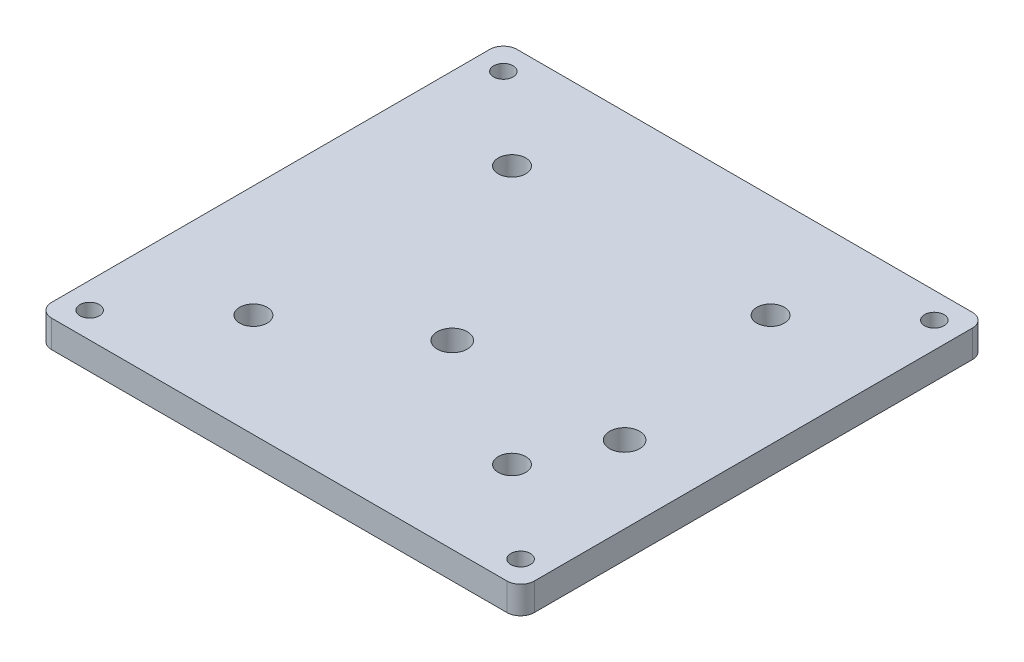
SolidWorks part; units mm, degrees
material "AISI 4130 Steel, annealed at 865C"
ref_plane "Front Plane" through (0, 0, 0) normal (0, 0, 1) x (1, 0, 0)
ref_plane "Top Plane" through (0, 0, 0) normal (0, 1, 0) x (1, 0, 0)
ref_plane "Right Plane" through (0, 0, 0) normal (1, 0, 0) x (0, 0, -1)
sketch "Sketch1" plane through (0, 0, 0) normal (0, 1, 0) x (1, 0, 0)
  line L0 (7, -7) -> (7, -37) construction
  line L1 (0, 0) -> (44, 0)
  line L2 (0, 0) -> (0, -44)
  line L3 (0, -44) -> (44, -44)
  line L4 (44, 0) -> (44, -44)
  line L5 (37, -7) -> (7, -7) construction
  line L6 (40, 2.5) -> (40, 0) construction
  line L7 (22, 0) -> (22, -44) construction
  line L8 (44, 0) -> (51.18, 0)
  line L9 (51.18, 0) -> (51.18, -44)
  line L10 (51.18, -44) -> (44, -44)
  line L11 (22, -22) -> (-15.2405, -22) construction
  line L12 (21.07, -28) -> (41.07, -28) construction
  line L13 (40, -46.5) -> (40, -44) construction
  line L15 (0, -44) -> (44, -44)
  line L16 (0, -44) -> (0, -49)
  line L17 (0, -49) -> (44, -49)
  line L18 (44, -44) -> (44, -49)
  line L19 (0, 0) -> (44, 0)
  line L20 (0, 0) -> (0, 5)
  line L21 (0, 5) -> (44, 5)
  line L22 (44, 0) -> (44, 5)
  circle A0 centre (7, -7) radius 1.6
  circle A1 centre (37, -7) radius 1.6
  circle A2 centre (37, -37) radius 1.6
  circle A3 centre (7, -37) radius 1.6
  circle A8 centre (21.07, -28) radius 1.75
  circle A9 centre (41.07, -28) radius 1.75
  circle A10 centre (40, 2.5) radius 0.5 construction
  circle A11 centre (40, -46.5) radius 0.5 construction
  circle A12 centre (4, 2.5) radius 0.5 construction
  circle A13 centre (4, -46.5) radius 0.5 construction
  point P37 (0, 0)
  point P38 (0, 0)
  point P39 (0, 0)
  point P40 (3.1693, -47)
  point P41 (3.2554, -47)
  point P42 (5.2345, 3)
  dimension "D1" = 3.2
  dimension "D13" = 3.5
  dimension "D10" = 1
  dimension "D3" = 30
  dimension "D4" = 30
  dimension "D6" = 44
  dimension "D7" = 44
  dimension "D8" = 7
  dimension "D9" = 7
  dimension "D11" = 7.18
  dimension "D14" = 20
  dimension "D5" = 0.93
  dimension "D2" = 6
  dimension "D15" = 4
  dimension "D16" = 5
  dimension "D17" = 4
  dimension "D12" = 2.5
extrude "Boss-Extrude1" add sketch "Sketch1" along normal blind 3.175 contours L1 L22 L21 L20 A12 A10 | L4 L1 L2 L3 A9 A8 A3 A2 A1 A0 | L18 L3 L16 L17 A13 A11 region at (22, 0, -2.5) region at (21.9074, 0, 21.9387) region at (22, 0, 46.5)
sketch "Sketch2" plane through (0, 3.175, 0) normal (0, 1, 0) x (1, 0, 0)
  line L1 (0, 5) -> (-6, 5)
  line L2 (0, 5) -> (0, -49)
  line L3 (0, -49) -> (-6, -49)
  line L4 (-6, 5) -> (-6, -49)
  line L5 (44, 5) -> (50, 5)
  line L6 (44, 5) -> (44, -49)
  line L7 (44, -49) -> (50, -49)
  line L8 (50, 5) -> (50, -49)
  circle A0 centre (47, 2) radius 2.3241 construction
  circle A1 centre (-3, 2) radius 2.3241 construction
  circle A2 centre (-3, -46) radius 2.3241 construction
  circle A3 centre (47, -46) radius 2.3241 construction
  point P10 (47, 2)
  point P12 (47, -46)
  point P14 (-3, 2)
  point P15 (-3, -46)
  line M18 (0, 5) -> (0, -49)
  line M26 (44, -49) -> (44, 5)
  dimension "D6" = 4.6482
  dimension "D1" = 6
  dimension "D2" = 3
  dimension "D3" = 3
  dimension "D4" = 3
  dimension "D5" = 3
extrude "Boss-Extrude2" add sketch "Sketch2" against normal up to surface (3.175 mm away) contours L1 L4 L3 M18 | L8 L5 L7 M26 region at (-3, 3.175, 22) region at (47, 3.175, 22) up to face at (22, 0, 22)
hole_wizard "#4-40 Tapped Hole1" positions "3DSketch1" profile "Sketch3" tap size "#4-40" standard "ANSI Inch" end condition through all
sketch3d "3DSketch1"
  point P3 (-3, 3.175, -2)
  point P6 (-3, 3.175, 46)
  point P9 (47, 3.175, -2)
  point P12 (47, 3.175, 46)
  point P15 (0, 0, 0)
  point P16 (4, 3.175, -2.5)
  point P19 (0, 0, 0)
  point P20 (0, 0, 0)
  point P21 (0, 0, 0)
  point P22 (4, 3.175, 46.5)
  point P25 (40, 3.175, 46.5)
  point P28 (40, 3.175, -2.5)
  point P31 (0, 0, 0)
  point P32 (-3, 3.175, -2)
  point P34 (0, 0, 0)
  point P35 (47, 3.175, -2)
  point P37 (0, 0, 0)
  point P38 (47, 3.175, 46)
  point P40 (0, 0, 0)
  point P41 (-3, 3.175, 46)
sketch "Sketch3" plane through (-3, 3.175, -2) normal (1, 0, 0) x (0, 0, 1)
  line L0 (0, 0) -> (0, 3.175)
  line L1 (0, 3.175) -> (1.1303, 3.175)
  line L2 (1.1303, 3.175) -> (1.1303, 0)
  line L5 (1.1303, 0) -> (0, 0)
  line L11 (0, -6.35) -> (0, 107.95) construction
  dimension "Thru Tap Drill Dia." = 2.2606
  dimension "Thru Tap Drill Depth" = 3.175
cosmetic thread "Hole Thread1" parameters "D2"=2.8448
cosmetic thread "Hole Thread2" parameters "D2"=2.8448
cosmetic thread "Hole Thread3" parameters "D2"=2.8448
cosmetic thread "Hole Thread4" parameters "D2"=2.8448
fillet "Fillet1" radius 1.5875 4 edges at (-6, 1.5875, -5) (50, 1.5875, -5) (50, 1.5875, 49) (-6, 1.5875, 49)
equation "\"D8@Sketch1\"=(\"D7@Sketch1\"-\"D4@Sketch1\")/2"
equation "\"D9@Sketch1\"=\"D8@Sketch1\""
equation "\"D3@Sketch2\"=\"D2@Sketch2\""
equation "\"D4@Sketch2\"=\"D2@Sketch2\""
equation "\"D5@Sketch2\"=\"D2@Sketch2\""
equation "\"D5@Sketch1\"=9.37mm-6.3-2-0.14"
equation "\"D17@Sketch1\"=\"D15@Sketch1\""
equation "\"D12@Sketch1\"=\"D16@Sketch1\"/2"
